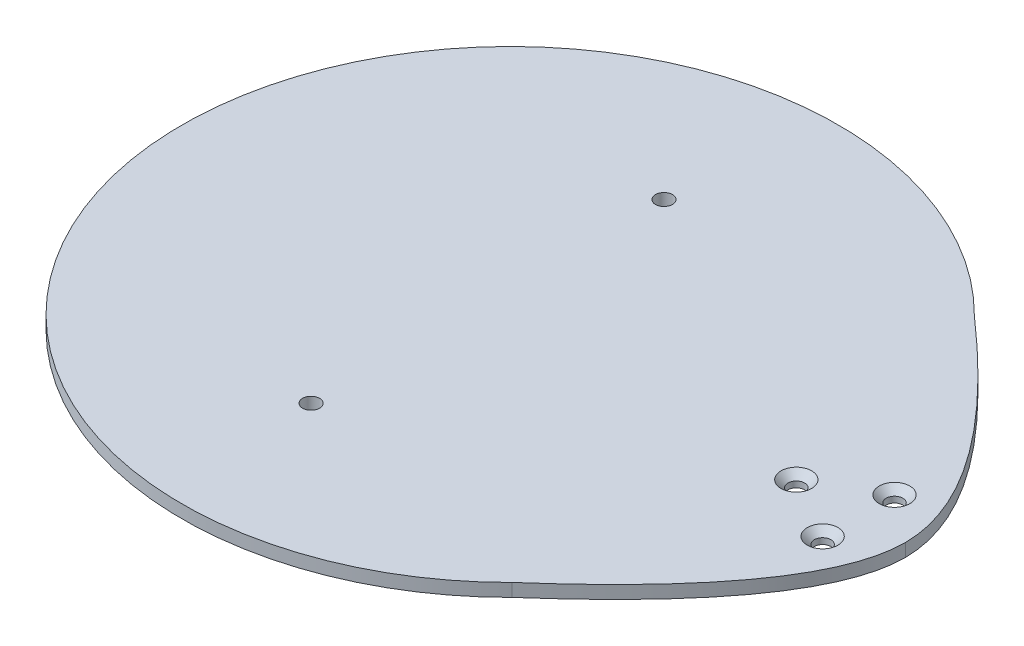
SolidWorks part; units mm, degrees
ref_plane "Ebene vorne" through (0, 0, 0) normal (0, 0, 1) x (1, 0, 0)
ref_plane "Ebene oben" through (0, 0, 0) normal (0, 1, 0) x (1, 0, 0)
ref_plane "Ebene rechts" through (0, 0, 0) normal (1, 0, 0) x (0, 0, -1)
sketch "Skizze1" plane through (0, 0, 0) normal (0, 1, 0) x (1, 0, 0)
  line L0 (28.9708, -44.5268) -> (28.9708, -44.5303)
  line L1 (60.1894, -0.0013) -> (47.1894, -0.0013) construction
  line L2 (47.1894, -0.0013) -> (-20.3106, -0.0013) construction
  arc A0 (28.9708, 44.5276) -> (28.9708, -44.5268) centre (-15.9502, 0.0004) ccw
  circle A1 centre (47.1894, -0.0013) radius 13
  spline S0 degree 2 poles (60.1894, -0.0013) (60.1894, 17.149) (28.9708, 44.5276) knots 0 0 0 1 1 1
  spline S1 degree 2 poles (60.1894, -0.0013) (60.1894, -17.1517) (28.9708, -44.5303) knots 0 0 0 1 1 1
  point P0 (0, 0)
  point P4 (0, 0)
  dimension "D1" = 13
  dimension "D2" = 67.5
extrude "Aufsatz-Linear austragen1" add sketch "Skizze1" along normal blind 2.5 contours S1 A1 S0 A0 L0 | A1 region at (-15.3772, 0, -0.0002) region at (47.1894, 0, 0.0013)
sketch "Skizze2" plane through (0, 2.5, 0) normal (0, 1, 0) x (1, 0, 0)
  line L0 (47.1894, -0.0013) -> (51.1894, 6.9269) construction
  line L1 (60.1894, -0.0013) -> (47.1894, -0.0013) construction
  circle A0 centre (47.1894, -0.0013) radius 3
  circle A1 centre (47.1894, -0.0013) radius 8
  circle A2 centre (51.1894, 6.9269) radius 1.6
  circle A3 centre (51.1894, -6.9296) radius 1.6
  circle A4 centre (39.1894, -0.0013) radius 1.6
  circle A5 centre (47.1894, -0.0013) radius 13
  point P13 (47.1894, -0.0013)
  dimension "D1" = 6
  dimension "D2" = 16
  dimension "D3" = 3.2
  dimension "D5" = 60
  dimension "D4" = 3
extrude "Schnitt-Linear austragen1" cut sketch "Skizze2" against normal through all contours A1 A2 | A2 L0 A1 | L0 A2 A1 | A1 A3 | A1 A3 | A1 A4 | A1 A4 region at (50.2677, 2.5, -6.6425) region at (51.4039, 2.5, -5.9865) region at (51.5141, 2.5, -7.4893) region at (39.8964, 2.5, 0.0013) region at (38.5399, 2.5, 0.0013) region at (51.5141, 2.5, 7.492) region at (50.8358, 2.5, 6.3172)
chamfer "Fase1" distance 1.35 angle 45 3 edges at (51.1894, 2.5, 8.5296) (39.1894, 2.5, 1.6013) (51.1894, 2.5, -5.3269)
sketch "Skizze3" plane through (0, 2.5, 0) normal (0, 1, 0) x (1, 0, 0)
  line L0 (-20.3106, -34.0013) -> (-20.3106, 33.9987)
  circle A0 centre (-20.3106, 33.9987) radius 1.65
  circle A1 centre (-20.3106, -34.0013) radius 1.65
  point P4 (-20.3106, -0.0013)
  point P7 (0, 0)
  dimension "D2" = 3.3
  dimension "D3" = 3.3
  dimension "D1" = 68
extrude "Schnitt-Linear austragen2" cut sketch "Skizze3" against normal through all contours A1 | A0 region at (-21.4444, 2.5, -35.1324) region at (-19.1769, 2.5, 32.8676)
